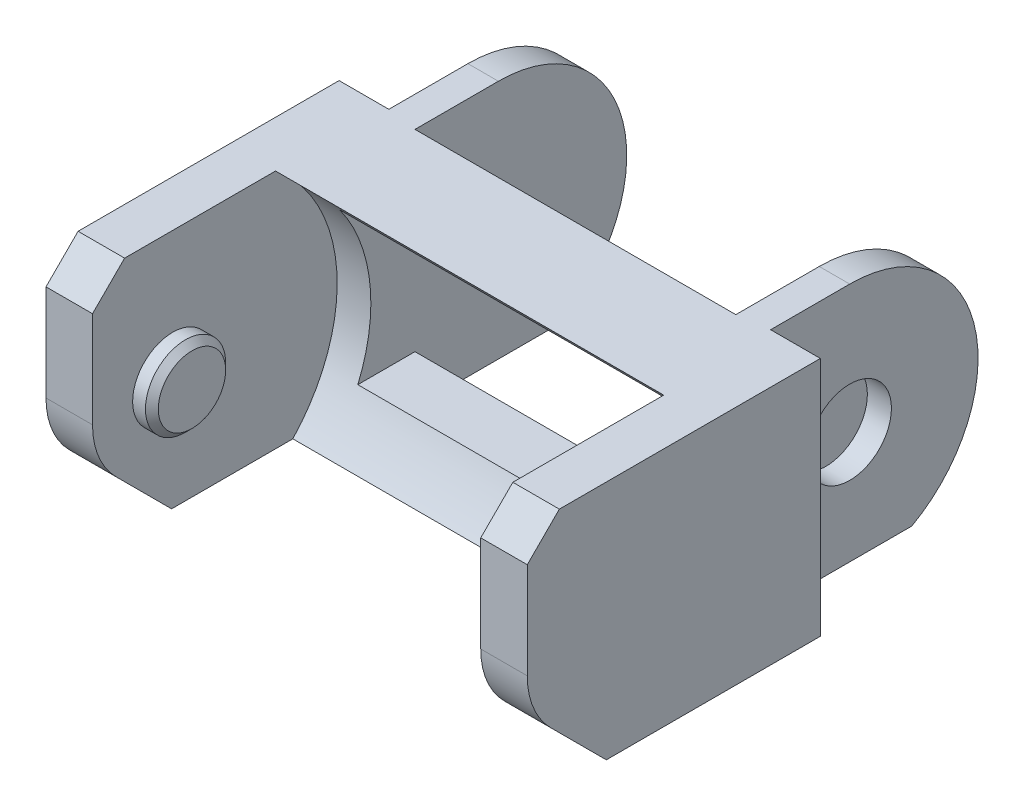
SolidWorks part; units mm, degrees
ref_plane "前基準面" through (0, 0, 0) normal (0, 0, 1) x (1, 0, 0)
ref_plane "上基準面" through (0, 0, 0) normal (0, 1, 0) x (1, 0, 0)
ref_plane "右基準面" through (0, 0, 0) normal (1, 0, 0) x (0, 0, -1)
sketch "草圖1" plane through (0, 0, 0) normal (0, 0, 1) x (1, 0, 0)
  line L1 (-12.751, 5.0503) -> (17.249, 5.0503)
  line L2 (-12.751, 5.0503) -> (-12.751, -9.9497)
  line L3 (-12.751, -9.9497) -> (17.249, -9.9497)
  line L4 (17.249, 5.0503) -> (17.249, -9.9497)
  dimension "D1" = 30
  dimension "D2" = 15
extrude "填料-伸長1" add sketch "草圖1" along normal blind 18
sketch "草圖2" plane through (0, 0, 18) normal (0, 0, 1) x (1, 0, 0)
  line L0 (-12.751, 5.0503) -> (-12.751, -9.9497) construction
  line L1 (-7.751, 3.0503) -> (12.249, 3.0503)
  line L2 (-7.751, 3.0503) -> (-7.751, -6.9497)
  line L3 (-7.751, -6.9497) -> (12.249, -6.9497)
  line L4 (12.249, 3.0503) -> (12.249, -6.9497)
  line L5 (17.249, -9.9497) -> (17.249, 5.0503) construction
  line L6 (17.249, 5.0503) -> (-12.751, 5.0503) construction
  line L7 (-12.751, -9.9497) -> (17.249, -9.9497) construction
  dimension "D1" = 5
  dimension "D2" = 5
  dimension "D3" = 2
  dimension "D4" = 3
extrude "除料-伸長1" cut sketch "草圖2" against normal up to next
sketch "草圖3" plane through (0, -6.9497, 0) normal (0, 1, 0) x (1, 0, 0)
  line L0 (-7.751, 0) -> (-7.751, -18) construction
  line L1 (-7.751, -6) -> (12.249, -6)
  line L2 (-7.751, -6) -> (-7.751, -18)
  line L3 (-7.751, -18) -> (12.249, -18)
  line L4 (12.249, -6) -> (12.249, -18)
  dimension "D1" = 12
extrude "除料-伸長2" cut sketch "草圖3" against normal up to next
sketch "草圖4" plane through (-7.751, 0, 0) normal (1, 0, 0) x (0, 0, -1)
  line L0 (-18, 3.0503) -> (-18, -9.9497) construction
  line L1 (-18, -9.9497) -> (-6, -9.9497) construction
  line L3 (-13, -2.9497) -> (-18, -2.9497)
  line L4 (-13, -2.9497) -> (-13, 7.8945)
  line L5 (-18, -2.9497) -> (-18, 7.8945)
  line L6 (-13, 7.8945) -> (-18, 7.8945)
  circle A0 centre (-13, -2.9497) radius 10.25
  line M3 (0, 3.0503) -> (-18, 3.0503)
  line M4 (-18, 3.0503) -> (-18, -9.9497)
  line M5 (-18, -9.9497) -> (-6, -9.9497)
  line M6 (-6, -9.9497) -> (-6, -6.9497)
  line M7 (-6, -6.9497) -> (0, -6.9497)
  dimension "D2" = 7
  dimension "D3" = 20.5
  dimension "D1" = 5
extrude "除料-伸長5" cut sketch "草圖4" against normal blind 2.1 and the other way blind 22.1 contours L3 L4 M3 M4 | A0 L4 L3 M7 M3 M4 M5 M6 | A0 L4 L6 L5 | A0 L4 M3 | L4 A0 L5 M3 | L5 A0 M7 M6 M5 M4 region at (-7.751, -3.92, 9.9772) region at (-7.751, 0.0503, 15.5) region at (-7.751, -6.4497, 18.275) region at (-7.751, 4.9834, 15.3602) region at (-7.751, 4.7846, 9.7748) region at (-7.751, 7.3136, 16.0262)
sketch "草圖5" plane through (14.349, 0, 0) normal (-1, 0, 0) x (0, 0, 1)
  circle A0 centre (13, -2.9497) radius 2.5
  arc A2 (6.592, 5.0503) -> (5.5125, -9.9497) centre (13, -2.9497) ccw construction
  dimension "D1" = 5
extrude "填料-伸長2" add sketch "草圖5" along normal blind 1.2
sketch "草圖6" plane through (-9.851, 0, 0) normal (1, 0, 0) x (0, 0, -1)
  circle A0 centre (-13, -2.9497) radius 2.5
  arc A1 (-5.5125, -9.9497) -> (-6.592, 5.0503) centre (-13, -2.9497) ccw construction
  dimension "D1" = 5
extrude "填料-伸長3" add sketch "草圖6" along normal blind 1.2
chamfer "導角1" distance 0.4 angle 45 2 edges at (-8.651, -0.4497, 13) (13.149, -5.4497, 13)
sketch "草圖7" plane through (-9.851, 0, 0) normal (1, 0, 0) x (0, 0, -1)
  line L0 (-13.0711, -9.9497) -> (-18, -5.0208)
  line L1 (-18, -9.9497) -> (-5.5125, -9.9497) construction
  line L2 (-18, -9.9497) -> (-18, 5.0503) construction
  circle A0 centre (-13, -2.9497) radius 2.5 construction
  line M4 (-18, 5.0503) -> (-18, -9.9497)
  line M5 (-18, -9.9497) -> (-5.5125, -9.9497)
  dimension "D1" = 45
  dimension "D2" = 5
extrude "除料-伸長6" cut sketch "草圖7" against normal through all both and the other way through all contours L0 M5 M4 region at (-9.851, -8.3067, 16.357)
sketch "草圖8" plane through (-9.851, 0, 0) normal (1, 0, 0) x (0, 0, -1)
  line L0 (-18, -5.0208) -> (-18, -2.9497)
  line L1 (-18, -5.0208) -> (-15.5355, -7.4853)
  line L2 (-13.0711, -9.9497) -> (-18, -5.0208) construction
  circle A0 centre (-13, -2.9497) radius 5
  line M1 (-18, -5.0208) -> (-13.0711, -9.9497)
  line M5 (-18, 5.0503) -> (-18, -5.0208)
extrude "除料-伸長7" cut sketch "草圖8" against normal through all both and the other way through all contours A0 M5 M1 region at (-9.851, -4.8962, 17.6992)
sketch "草圖9" plane through (0, 0, 0) normal (0, 0, -1) x (-1, 0, 0)
  line L0 (-17.249, 5.0503) -> (12.751, 5.0503) construction
  line L1 (-12.249, 5.0503) -> (7.751, 5.0503)
  line L2 (-12.249, 5.0503) -> (-12.249, -9.9497)
  line L3 (-12.249, -9.9497) -> (7.751, -9.9497)
  line L4 (7.751, 5.0503) -> (7.751, -9.9497)
  line L5 (12.751, -9.9497) -> (-17.249, -9.9497) construction
  line L6 (-12.249, 3.0503) -> (-12.249, -6.9497) construction
  line L7 (9.651, -9.9497) -> (-14.149, -9.9497)
  line L8 (9.651, -9.9497) -> (9.651, 5.0503)
  line L9 (9.651, 5.0503) -> (-14.149, 5.0503)
  line L10 (-14.149, -9.9497) -> (-14.149, 5.0503)
  line L11 (7.751, -6.9497) -> (7.751, 3.0503) construction
  line M6 (7.751, 3.0503) -> (7.751, -6.9497)
  line M8 (-12.249, -6.9497) -> (-12.249, 3.0503)
  line M10 (12.751, 5.0503) -> (-17.249, 5.0503)
  line M12 (-17.249, -9.9497) -> (12.751, -9.9497)
  dimension "D1" = 1.9
  dimension "D2" = 1.9
extrude "填料-伸長4" add sketch "草圖9" along normal blind 20 contours L8 L4 M12 M10 M6 | L10 L2 M12 M8 M10 region at (13.199, -2.4497, 0) region at (-8.701, -2.4497, 0)
sketch "草圖10" plane through (14.149, 0, 0) normal (1, 0, 0) x (0, 0, -1)
  line L0 (0, -9.9497) -> (0, 5.0503) construction
  line L1 (20, -9.9497) -> (0, -9.9497) construction
  circle A0 centre (5.2, -2.9497) radius 2.6
  dimension "D1" = 5.2
  dimension "D2" = 5.2
  dimension "D3" = 7
extrude "除料-伸長8" cut sketch "草圖10" against normal through all
sketch "草圖12" plane through (14.149, 0, 0) normal (1, 0, 0) x (0, 0, -1)
  line L1 (5.2, 5.0503) -> (18.304, 5.0503)
  line L2 (5.2, 5.0503) -> (5.2, -15.4926)
  line L3 (5.2, -15.4926) -> (18.304, -15.4926)
  line L4 (18.304, 5.0503) -> (18.304, -15.4926)
  circle A0 centre (5.2, -2.9497) radius 8
  line M3 (0, -9.9497) -> (20, -9.9497)
  line M4 (20, -9.9497) -> (20, 5.0503)
  line M5 (20, 5.0503) -> (0, 5.0503)
extrude "除料-伸長9" cut sketch "草圖12" against normal through all both and the other way through all contours A0 L4 M3 M5 | L4 M5 M3 M4 region at (14.149, -2.1497, -14.8341) region at (14.149, -2.4497, -19.152)
sketch "草圖15" plane through (12.249, 0, 0) normal (1, 0, 0) x (0, 0, -1)
  circle A0 centre (5.2, -2.9497) radius 2.6
extrude "填料-伸長6" add sketch "草圖15" along normal blind 0.4
sketch "草圖16" plane through (-7.751, 0, 0) normal (-1, 0, 0) x (0, 0, 1)
  circle A0 centre (-5.2, -2.9497) radius 2.6
extrude "填料-伸長7" add sketch "草圖16" along normal blind 0.4
chamfer "導角2" distance 2 angle 45 2 edges at (15.799, 5.0503, 18) (-11.301, 5.0503, 18)
sketch "草圖17" plane through (0, 0, 0) normal (0, 0, -1) x (-1, 0, 0)
  line L1 (-17.249, 5.0503) -> (-14.149, 5.0503)
  line L2 (-17.249, 5.0503) -> (-17.249, -9.9497)
  line L3 (-17.249, -9.9497) -> (-14.149, -9.9497)
  line L4 (-14.149, 5.0503) -> (-14.149, -9.9497)
  line L5 (9.651, 5.0503) -> (12.751, 5.0503)
  line L6 (9.651, 5.0503) -> (9.651, -9.9497)
  line L7 (9.651, -9.9497) -> (12.751, -9.9497)
  line L8 (12.751, 5.0503) -> (12.751, -9.9497)
extrude "填料-伸長8" add sketch "草圖17" along normal blind 0.27
